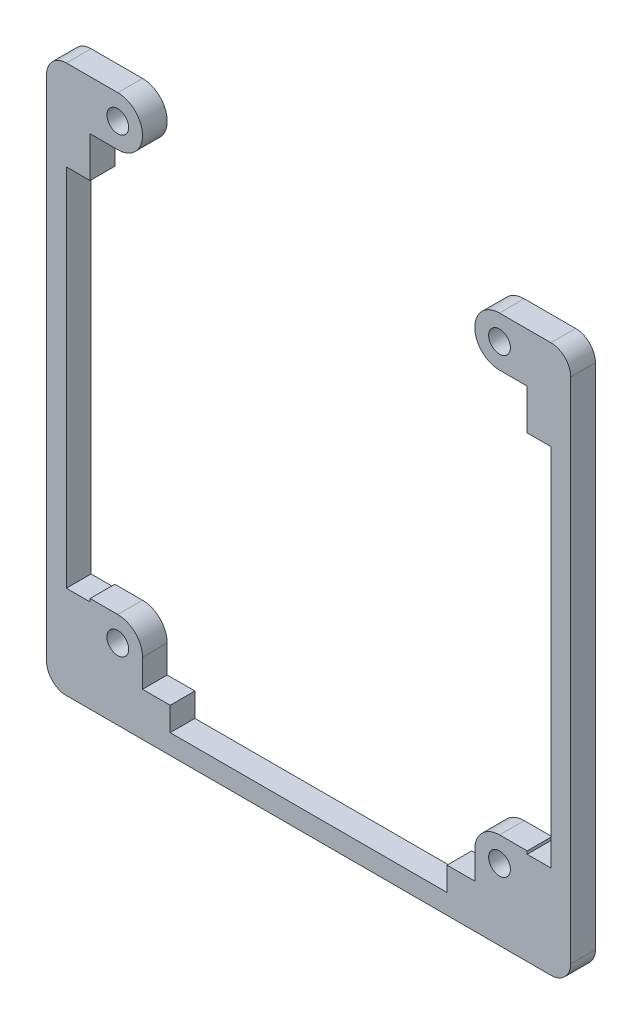
SolidWorks part; units mm, degrees
ref_plane "Front Plane" through (0, 0, 0) normal (0, 0, 1) x (1, 0, 0)
ref_plane "Top Plane" through (0, 0, 0) normal (0, 1, 0) x (1, 0, 0)
ref_plane "Right Plane" through (0, 0, 0) normal (1, 0, 0) x (0, 0, -1)
sketch "Sketch1" plane through (0, 0, 0) normal (0, 0, 1) x (1, 0, 0)
  line L1 (0, 6.35) -> (0, 53.213) construction
  line L2 (3.048, 6.35) -> (3.048, 53.213) construction
  line L3 (3.048, 6.35) -> (0, 6.35) construction
  line L4 (-59.182, 6.35) -> (-56.134, 6.35) construction
  line L7 (-59.182, 53.213) -> (-56.134, 53.213) construction
  line L8 (-45.847, -3.048) -> (-45.847, 0) construction
  line L9 (-10.287, 0) -> (-45.847, 0) construction
  line L10 (-10.287, -3.048) -> (-45.847, -3.048) construction
  line L11 (-10.287, -3.048) -> (-10.287, 0) construction
  line L12 (0, 53.213) -> (3.048, 53.213)
  line L13 (0, 6.35) -> (0, 53.213)
  line L14 (3.048, 6.35) -> (3.048, 53.213)
  line L15 (3.048, 6.35) -> (0, 6.35)
  line L16 (-59.182, 6.35) -> (-56.134, 6.35)
  line L17 (-59.182, 6.35) -> (-59.182, 53.213)
  line L18 (-56.134, 6.35) -> (-56.134, 53.213)
  line L19 (-59.182, 53.213) -> (-56.134, 53.213)
  line L20 (-45.847, -3.048) -> (-45.847, 0)
  line L21 (-10.287, 0) -> (-45.847, 0)
  line L22 (-10.287, -3.048) -> (-45.847, -3.048)
  line L23 (-10.287, -3.048) -> (-10.287, 0)
  line L24 (-28.067, 0) -> (-28.067, 55.1636) construction
  line L25 (-3.556, 61.595) -> (-3.556, 3.556) construction
  line L26 (-52.578, 61.595) -> (-52.578, 3.556) construction
  line L27 (-52.578, 58.42) -> (-56.134, 58.42)
  line L28 (-59.182, 64.77) -> (3.048, 64.77)
  line L29 (-61.722, 62.23) -> (-61.722, -3.048)
  line L30 (-59.182, -5.588) -> (3.048, -5.588)
  line L31 (5.588, 62.23) -> (5.588, -3.048)
  line L33 (-56.134, 58.42) -> (-56.134, 53.213)
  line L34 (-52.578, 6.731) -> (-56.134, 6.731)
  line L35 (-49.403, 3.556) -> (-49.403, 0)
  line L36 (-45.847, 0) -> (-59.182, 0) construction
  line L37 (-49.403, 0) -> (-45.847, 0)
  line L38 (-10.287, 0) -> (-6.731, 0)
  line L39 (3.048, 0) -> (-10.287, 0) construction
  line L40 (-6.731, 0) -> (-6.731, 3.556)
  line L41 (-3.556, 6.731) -> (0, 6.731)
  line L42 (-3.556, 58.42) -> (0, 58.42)
  line L44 (0, 58.42) -> (0, 53.213)
  line L46 (-56.134, 6.731) -> (-56.134, 6.35)
  line L47 (0, 6.35) -> (0, 6.731)
  line L48 (-6.731, 0) -> (-10.287, 0)
  circle A0 centre (-3.556, 3.556) radius 1.397
  circle A1 centre (-3.556, 61.595) radius 1.397
  circle A2 centre (-52.578, 61.595) radius 1.397
  circle A3 centre (-52.578, 3.556) radius 1.397
  circle A4 centre (-52.578, 61.595) radius 3.175
  circle A5 centre (-52.578, 3.556) radius 3.175
  circle A6 centre (-3.556, 61.595) radius 3.175
  circle A7 centre (-3.556, 3.556) radius 3.175
  arc A8 (-61.722, -3.048) -> (-59.182, -5.588) centre (-59.182, -3.048) ccw
  arc A9 (3.048, -5.588) -> (5.588, -3.048) centre (3.048, -3.048) ccw
  arc A10 (3.048, 64.77) -> (5.588, 62.23) centre (3.048, 62.23) cw
  arc A11 (-59.182, 64.77) -> (-61.722, 62.23) centre (-59.182, 62.23) ccw
  dimension "D1" = 2.159
  dimension "D2" = 2.794
  dimension "D3" = 2.159
  dimension "D4" = 55.245
  dimension "D5" = 6.35
  dimension "D9" = 2.54
  dimension "D6" = 2.54
  dimension "D7" = 2.54
  dimension "D8" = 2.54
extrude "Boss-Extrude1" add sketch "Sketch1" along normal blind 3.175 contours L28 A11 L29 A8 L30 A9 L31 A10 A6 L42 L44 L14 L15 L13 L41 A7 L40 L38 L23 L22 L20 L37 L35 A5 L18 L16 L17 L19 L33 L27 A4 | A4 A2 | A6 A1 | A5 A3 | A7 A0 region at (0.9737, 55.8165, 0) region at (-1.3744, 5.7376, 0) region at (-6.6412, 61.595, 0) region at (-50.3964, 63.7766, 0) region at (-54.7596, 1.3744, 0)
